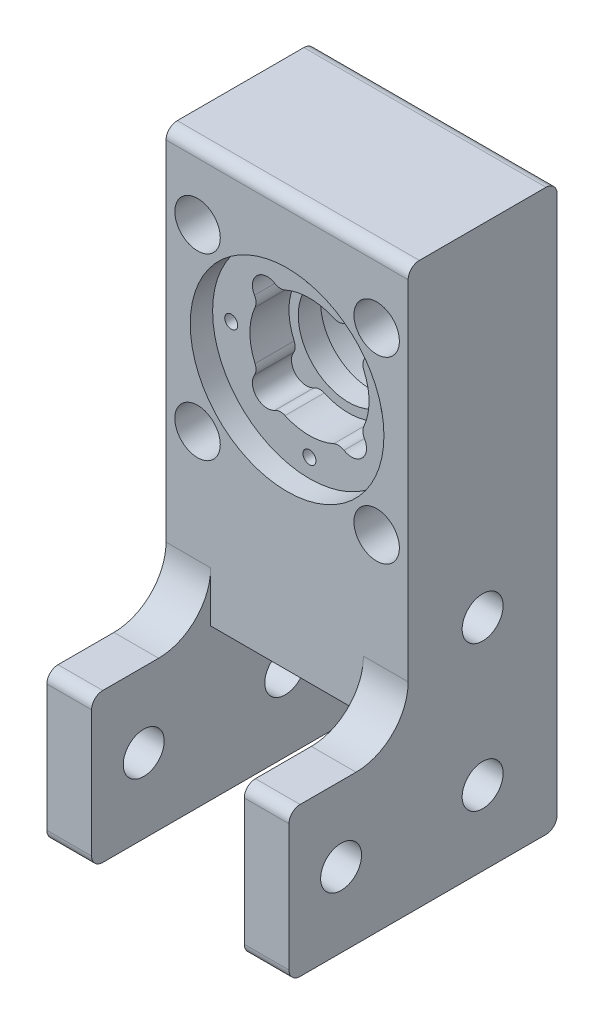
SolidWorks part; units mm, degrees
ref_plane "Front plane" through (0, 0, 0) normal (0, 0, 1) x (1, 0, 0)
ref_plane "Top plane" through (0, 0, 0) normal (0, 1, 0) x (1, 0, 0)
ref_plane "Right plane" through (0, 0, 0) normal (1, 0, 0) x (0, 0, -1)
ref_axis "Axis X" through (0, 0, 0) along (1, 0, 0)
ref_axis "Axis Y" through (0, 0, 0) along (0, 1, 0)
ref_axis "Axis Z" through (0, 0, 0) along (0, 0, 1)
sketch "Sketch1" plane through (0, 0, 0) normal (1, 0, 0) x (0, 0, -1)
  line L1 (10, 65.25) -> (-10, 65.25)
  line L2 (10, 65.25) -> (10, 10.25)
  line L3 (10, 10.25) -> (-10, 10.25)
  line L4 (-10, 65.25) -> (-10, 10.25)
  line L5 (10, 65.25) -> (-10, 10.25) construction
  line L6 (10, 10.25) -> (-10, 65.25) construction
  point P0 (0, 37.75)
  dimension "D1" = 10.25
  dimension "D2" = 20
  dimension "D3" = 55
extrude "Extrude1" add sketch "Sketch1" along normal blind 10.25 and the other way blind 10.25
sketch "Sketch2" plane through (10.25, 0, 0) normal (1, 0, 0) x (0, 0, -1)
  line L0 (10, 10.25) -> (10, 65.25) construction
  line L1 (26, 10) -> (17, 10)
  line L2 (26, 10) -> (26, -10)
  line L3 (26, -10) -> (-26, -10)
  line L4 (-26, 10) -> (-26, -10)
  line L5 (26, 10) -> (-26, -10) construction
  line L6 (26, -10) -> (-26, 10) construction
  line L7 (-10, 65.25) -> (10, 65.25)
  line L8 (-10, 65.25) -> (-10, 17)
  line L9 (-10, 10) -> (10, 10) construction
  line L10 (10, 65.25) -> (10, 17)
  line L11 (-17, 10) -> (-26, 10)
  line L12 (10, 10) -> (-10, 10) construction
  arc A0 (17, 10) -> (10, 17) centre (17, 17) cw
  arc A1 (-17, 10) -> (-10, 17) centre (-17, 17) ccw
  point P0 (0, 0)
  dimension "D3" = 7
  dimension "D1" = 20
  dimension "D2" = 52
extrude "Extrude2" add sketch "Sketch2" along normal blind 6
mirror "Mirror2" about plane through (0, 0, 0) normal (1, 0, 0) of "Extrude2"
sketch "Sketch4" plane through (16.25, 0, 0) normal (1, 0, 0) x (0, 0, -1)
  line L0 (0, 2.75) -> (0, -2.75) construction
  circle A0 centre (0, 0) radius 2.75
  circle A1 centre (19, 0) radius 2.75
  circle A2 centre (-19, 0) radius 2.75
  circle A3 centre (0, 19.5) radius 2.75
  circle A4 centre (0, 51.75) radius 2.75 construction
  dimension "D1" = 5.5
  dimension "D2" = 5.5
  dimension "D4" = 5.5
  dimension "D5" = 5.5
  dimension "D3" = 19
  dimension "D6" = 32.25
  dimension "D7" = 19.5
extrude "Extrude3" cut sketch "Sketch4" against normal through all
sketch "Sketch5" plane through (0, 0, 10) normal (0, 0, 1) x (1, 0, 0)
  line L0 (-16.25, 19.5) -> (16.25, 19.5) construction
  line L1 (-16.25, 65.25) -> (-16.25, 17) construction
  line L2 (16.25, 65.25) -> (16.25, 17) construction
  line L3 (-16.25, 22.25) -> (16.25, 22.25) construction
  line L4 (-16.25, 16.75) -> (16.25, 16.75) construction
  line L5 (-16.25, 54.5) -> (16.25, 54.5) construction
  line L6 (-16.25, 51.75) -> (16.25, 51.75) construction
  line L7 (-16.25, 49) -> (16.25, 49) construction
  line L8 (-6.755, 44) -> (6.755, 44) construction
  line L9 (-10.25, 10) -> (10.25, 10) construction
  line L10 (-10.25, 10) -> (-10.25, -10) construction
  line L11 (10.25, 10) -> (10.25, -10) construction
  circle A0 centre (0, 44) radius 6.755
  dimension "D1" = 5.5
  dimension "D2" = 5.5
  dimension "D5" = 13.51
  dimension "D3" = 19.5
  dimension "D4" = 32.25
  dimension "D7" = 10
  dimension "D8" = 34
extrude "Extrude4" cut sketch "Sketch5" against normal through all
fillet "Fillet2" radius 1.5 10 edges at (13.25, -10, 26) (13.25, 10, 26) (-13.25, 10, 26) (-13.25, -10, 26) (-13.25, -10, -26) (13.25, -10, -26) (13.25, 10, -26) (-13.25, 10, -26) (0, 65.25, 10) (0, 65.25, -10)
sketch "Эскиз1" plane through (0, 0, -10) normal (0, 0, -1) x (-1, 0, 0)
  line L0 (-16.25, 17) -> (-16.25, 63.75) construction
  line L1 (16.25, -10) -> (-16.25, -10)
  line L2 (16.25, -10) -> (16.25, 63.75)
  line L3 (16.25, 63.75) -> (-16.25, 63.75)
  line L4 (-16.25, -10) -> (-16.25, 63.75)
  line L5 (16.25, -10) -> (-16.25, 63.75) construction
  line L6 (16.25, 63.75) -> (-16.25, -10) construction
  line L7 (16.25, 17) -> (16.25, 63.75) construction
  line L8 (16.25, 63.75) -> (-16.25, 63.75) construction
  line L9 (-10.25, -10) -> (-16.25, -10) construction
  point P0 (0, 26.875)
extrude "Вырез-Вытянуть1" cut sketch "Эскиз1" along normal through all
fillet "Скругление1" radius 1.5 2 edges at (13.25, -10, -10) (-13.25, -10, -10)
sketch "Эскиз2" plane through (0, 0, 10) normal (0, 0, 1) x (1, 0, 0)
  circle A0 centre (0, 44) radius 13
  dimension "D1" = 26
extrude "Вырез-Вытянуть2" cut sketch "Эскиз2" against normal blind 3
sketch "Эскиз3" plane through (0, 0, 7) normal (0, 0, 1) x (1, 0, 0)
  circle A0 centre (0, 44) radius 8
  arc A1 (-1.9843, 51.75) -> (1.9843, 51.75) centre (0, 52) cw construction
  arc A2 (4.077, 50.8832) -> (6.8832, 48.077) centre (5.6569, 49.6569) cw
  arc A3 (7.75, 45.9843) -> (7.75, 42.0157) centre (8, 44) cw construction
  arc A4 (6.8832, 39.923) -> (4.077, 37.1168) centre (5.6569, 38.3431) cw
  arc A5 (1.9843, 36.25) -> (-1.9843, 36.25) centre (0, 36) cw construction
  arc A6 (-4.077, 37.1168) -> (-6.8832, 39.923) centre (-5.6569, 38.3431) cw
  arc A7 (-7.75, 42.0157) -> (-7.75, 45.9843) centre (-8, 44) cw construction
  arc A8 (-6.8832, 48.077) -> (-4.077, 50.8832) centre (-5.6569, 49.6569) cw
  circle M11 centre (0, 44) radius 6.755
  dimension "D1" = 16
  dimension "D2" = 2
  dimension "D3" = 8
extrude "Вырез-Вытянуть3" cut sketch "Эскиз3" against normal blind 5.25 contours A0 M11 | A8 A0 | A2 A0 | A4 A0 | A6 A0 region at (7.4975, 41.9462, 7) region at (6.2241, 50.2241, 7) region at (6.2241, 37.7759, 7) region at (-6.2241, 50.2241, 7) region at (-6.2241, 37.7759, 7)
fillet "Скругление2" radius 1.5 8 edges at (-6.8832, 48.077, 4.375) (-6.8832, 39.923, 4.375) (6.8832, 39.923, 4.375) (6.8832, 48.077, 4.375) (4.077, 50.8832, 4.375) (-4.077, 50.8832, 4.375) (4.077, 37.1168, 4.375) (-4.077, 37.1168, 4.375)
sketch "Эскиз4" plane through (0, 0, -10) normal (0, 0, -1) x (-1, 0, 0)
  circle A0 centre (0, 44) radius 10
  dimension "D1" = 20
extrude "Вырез-Вытянуть4" cut sketch "Эскиз4" against normal offset from surface (8.75 mm away) 3 up to face at (6.755, 44, 1.75)
sketch "Эскиз5" plane through (0, 0, 7) normal (0, 0, 1) x (1, 0, 0)
  circle A0 centre (0, 44) radius 10.5 construction
  circle A1 centre (0, 54.5) radius 0.875
  circle A2 centre (10.5, 44) radius 0.875
  circle A3 centre (0, 33.5) radius 0.875
  circle A4 centre (-10.5, 44) radius 0.875
  dimension "D1" = 21
  dimension "D2" = 1.75
  dimension "D3" = 4
extrude "Вырез-Вытянуть5" cut sketch "Эскиз5" against normal blind 8
sketch "Эскиз7" plane through (0, 0, 10) normal (0, 0, 1) x (1, 0, 0)
  line L1 (-12.0208, 56.0208) -> (12.0208, 56.0208) construction
  line L2 (-12.0208, 56.0208) -> (-12.0208, 31.9792) construction
  line L3 (-12.0208, 31.9792) -> (12.0208, 31.9792) construction
  line L4 (12.0208, 56.0208) -> (12.0208, 31.9792) construction
  line L5 (-12.0208, 56.0208) -> (12.0208, 31.9792) construction
  line L6 (-12.0208, 31.9792) -> (12.0208, 56.0208) construction
  circle A0 centre (0, 44) radius 17 construction
  circle A1 centre (-12.0208, 56.0208) radius 1.75
  circle A2 centre (12.0208, 56.0208) radius 1.75
  circle A3 centre (0, 44) radius 17 construction
  circle A4 centre (12.0208, 31.9792) radius 1.75
  circle A5 centre (0, 44) radius 17 construction
  circle A6 centre (-12.0208, 31.9792) radius 1.75
  circle A7 centre (0, 44) radius 17 construction
  dimension "D3" = 4
  dimension "D1" = 34
  dimension "D2" = 3.5
extrude "Вырез-Вытянуть6" cut sketch "Эскиз7" against normal through all
sketch "Эскиз8" plane through (0, 0, 10) normal (0, 0, 1) x (1, 0, 0)
  circle A0 centre (-12.0208, 56.0208) radius 3.05
  circle A1 centre (0, 44) radius 17 construction
  circle A2 centre (12.0208, 56.0208) radius 3.05
  circle A3 centre (12.0208, 31.9792) radius 3.05
  circle A4 centre (-12.0208, 31.9792) radius 3.05
  dimension "D1" = 6.1
extrude "Вырез-Вытянуть7" cut sketch "Эскиз8" against normal offset from surface (5 mm away) 15 up to face at (-10.2708, 31.9792, -10)
equation "\"print_offset\"= 0.5"
equation "\"prof_width\"= 20'Aluminium profile parameters"
equation "\"D1@Sketch1\"=(\"prof_width\"+\"print_offset\")/2"
equation "\"D3@Sketch1\" = 55.00"
equation "\"D1@Extrude1\"=(\"prof_width\"+\"print_offset\")/2"
equation "\"D2@Extrude1\"=(\"prof_width\"+\"print_offset\")/2"
equation "\"D1@Sketch2\"=\"prof_width\""
equation "\"D1@Sketch4\"=\"print_offset\"+5"
equation "\"D2@Sketch4\"=\"D1@Sketch4\""
equation "\"D4@Sketch4\"=\"D1@Sketch4\""
equation "\"D5@Sketch4\"=\"D1@Sketch4\""
equation "\"D2@Sketch5\"=\"D1@Sketch5\""
equation "\"D1@Sketch5\" = \"print_offset\" + 5.00"
equation "\"D7@Sketch5\"=\"prof_width\"/2"
equation "\"radial_bearing_d1\"= 7.7"
equation "\"radial_bearing_d2\"= 16"
equation "\"radial_bearing_h\"= 5"
equation "\"shaft_d\"= 6"
equation "\"shaft_h\" = 60"
equation "\"central_hole_d\"= 20"
equation "\"sitting_screws_d\"= 34"
equation "\"screw_d\"= 2"
equation "\"screw_hh_d\"= 3.4"
equation "\"screw_h\"= 8"
equation "\"screw_hh_h\"= 2"
equation "\"motor_screw_d\"= 3"
equation "\"motor_screw_hh_d\"= 5.6"
equation "\"motor_screw_h\" = 20"
equation "\"motor_screw_hh_h\"= 2"
equation "\"motor_nut_d\"= 5.4"
equation "\"motor_nut_h\"= 2.8"
equation "\"D1@Эскиз2\"=\"radial_bearing_d2\"+10"
equation "\"D1@Эскиз3\"=\"radial_bearing_d2\""
equation "\"D1@Вырез-Вытянуть3\"=\"radial_bearing_h\"+\"print_offset\"/2"
equation "\"D1@Эскиз4\"=\"central_hole_d\""
equation "\"D1@Эскиз5\"=\"radial_bearing_d2\"+5"
equation "\"D2@Эскиз5\"=\"screw_d\"-\"print_offset\"/2"
equation "\"D1@Вырез-Вытянуть5\"=\"screw_h\""
equation "\"D1@Эскиз7\"=\"sitting_screws_d\""
equation "\"D2@Эскиз7\"=\"motor_screw_d\"+\"print_offset\""
equation "\"D1\" = \"motor_screw_h\" - 5"
equation "\"D1@Эскиз8\"=\"motor_screw_hh_d\"+\"print_offset\""
equation "\"D1@Вырез-Вытянуть7\"=\"motor_screw_h\"-5"
equation "\"D5@Sketch5\"=\"radial_bearing_d2\"-(\"radial_bearing_d2\"-\"radial_bearing_d1\")*0.3"
